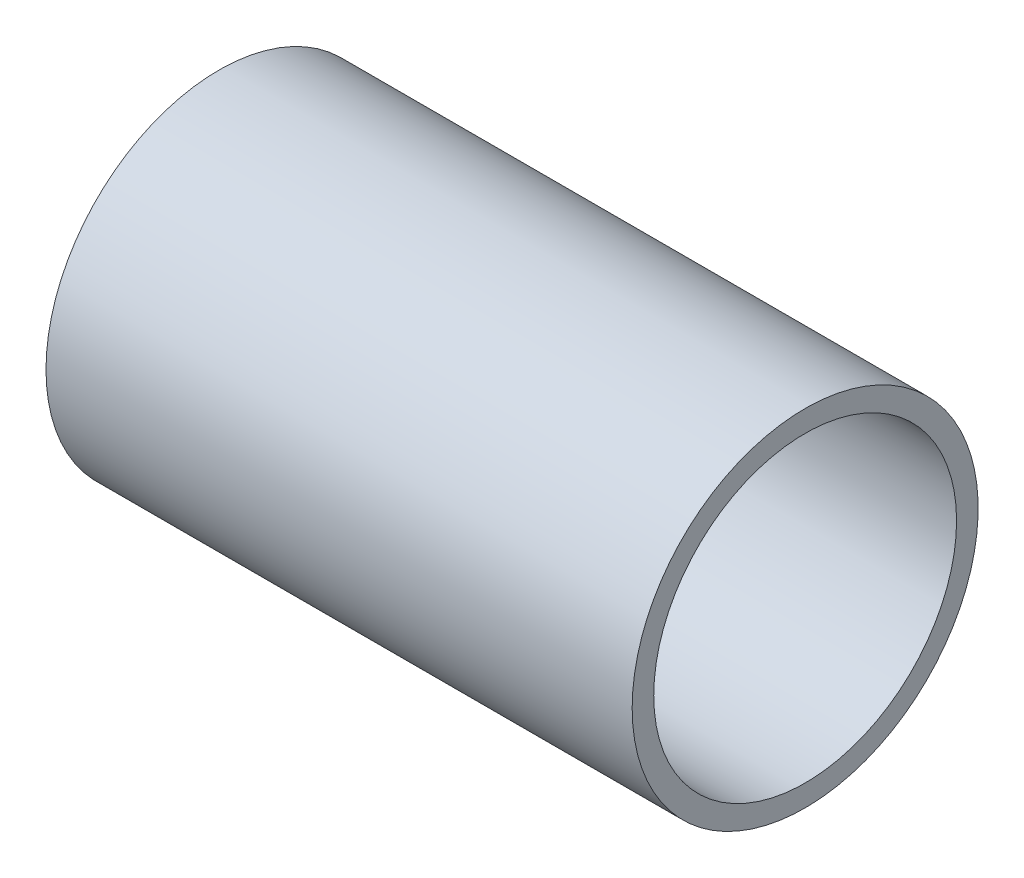
SolidWorks part; units mm, degrees
material "PE High Density"
ref_plane "Front Plane" through (0, 0, 0) normal (0, 0, 1) x (1, 0, 0)
ref_plane "Top Plane" through (0, 0, 0) normal (0, 1, 0) x (1, 0, 0)
ref_plane "Right Plane" through (0, 0, 0) normal (1, 0, 0) x (0, 0, -1)
sketch "Sketch2" plane through (0, 0, 0) normal (0, 0, 1) x (1, 0, 0)
  line L0 (0, 0) -> (74.8146, 0) construction
  line L2 (0, 141.732) -> (548.64, 141.732)
  line L3 (0, 141.732) -> (0, 161.925)
  line L4 (0, 161.925) -> (548.64, 161.925)
  line L5 (548.64, 141.732) -> (548.64, 161.925)
  dimension "D1" = 141.732
  dimension "D3" = 548.64
  dimension "D2" = 161.925
revolve "Revolve1" add sketch "Sketch2" angle 360 about L0
ref_plane "Midplane" through (274.32, 0, 0) normal (-1, 0, 0) x (0, 0, 1)
equation "\"ID\"= 11.160in"
equation "\"OD\"= 12.75in"
equation "\"Length\" = 21.6in"
equation "\"D1@Sketch2\"=\"ID\"/2"
equation "\"D3@Sketch2\"=\"Length\""
equation "\"D2@Sketch2\"=\"OD\"/2"
